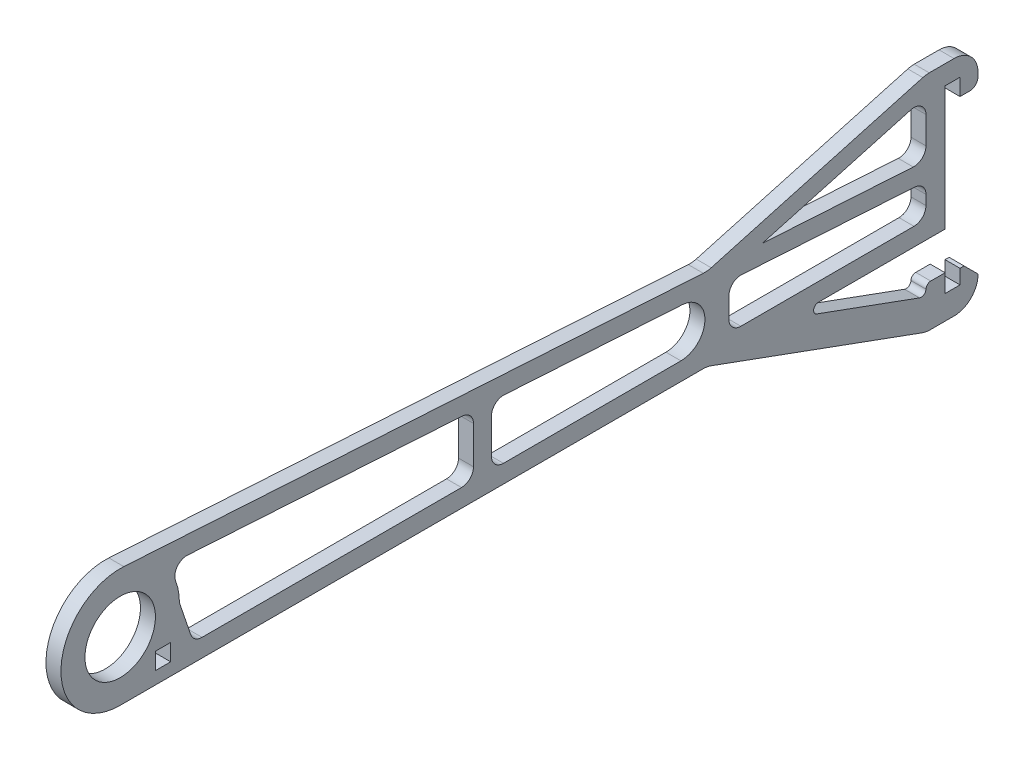
SolidWorks part; units mm, degrees
material "Delrin"
ref_plane "Front Plane" through (0, 0, 0) normal (0, 0, 1) x (1, 0, 0)
ref_plane "Top Plane" through (0, 0, 0) normal (0, 1, 0) x (1, 0, 0)
ref_plane "Right Plane" through (0, 0, 0) normal (1, 0, 0) x (0, 0, -1)
sketch "Sketch1" plane through (0, 0, 0) normal (1, 0, 0) x (0, 0, -1)
  line L0 (0.3859, 6.2619) -> (62.1851, 2.453)
  line L1 (0, -6.2738) -> (62.1851, -6.2738)
  line L2 (85.344, 8.8996) -> (88.3158, 8.8996)
  line L3 (4.7629, 4.0835) -> (85.344, -0.883)
  line L4 (4.5027, -4.3688) -> (85.344, -4.3688)
  line L5 (4.101, 4.1243) -> (87.7175, -1.0293) construction
  line L6 (0, -4.3688) -> (85.344, -4.3688) construction
  line L7 (85.344, -6.2738) -> (85.344, 8.8996) construction
  line L16 (6.2738, 0) -> (7.7597, -4.3688)
  line L17 (39.3251, 1.9533) -> (39.3251, -4.3688)
  line L18 (37.4201, 2.0707) -> (37.4201, -4.3688)
  line L23 (4.2182, 6.0257) -> (87.8347, 0.8721) construction
  line L24 (89.9668, 5.0896) -> (88.9508, 5.0896)
  line L25 (88.9508, 5.0896) -> (88.9508, 6.8676)
  line L26 (88.9508, 6.8676) -> (87.376, 6.8676)
  line L27 (87.376, 6.8676) -> (87.376, -6.2738)
  line L28 (87.376, -12.1824) -> (88.9508, -12.1824)
  line L29 (88.9508, -12.1824) -> (88.9508, -10.6584)
  line L30 (88.9508, -10.6584) -> (89.3826, -10.6584)
  line L31 (90.8558, -12.1316) -> (90.8558, -12.1824)
  line L32 (88.3158, -14.7224) -> (85.344, -14.7224)
  line L33 (85.344, -14.7224) -> (85.344, -6.2738) construction
  line L34 (90.8558, 5.9786) -> (90.8558, 6.3596)
  line L35 (89.3826, -10.6584) -> (90.8558, -12.1316)
  line L36 (64.4711, 0.4035) -> (64.4711, -4.3688)
  line L37 (62.1851, 0.5444) -> (62.1851, -4.3688)
  line L38 (62.1851, 2.453) -> (85.344, 8.8996)
  line L39 (68.0011, 2.0945) -> (85.344, 6.9222)
  line L40 (62.1851, -6.2738) -> (85.344, -14.7224)
  line L41 (71.0788, -6.2738) -> (85.344, -11.4779)
  line L42 (63.2297, -3.4104) -> (86.3886, -11.859) construction
  line L43 (62.696, 0.6178) -> (85.8549, 7.0644) construction
  line L44 (71.0788, -6.2738) -> (85.344, -6.2738)
  line L45 (0, -6.2738) -> (85.344, -6.2738) construction
  line L46 (68.0011, 2.0945) -> (85.344, 1.0256)
  line L47 (62.1851, -4.3688) -> (62.1851, 49995.6312) construction
  line L48 (85.344, 6.9222) -> (85.344, 1.0256)
  line L49 (85.344, -0.883) -> (85.344, -4.3688)
  line L50 (87.376, -12.1824) -> (87.376, -10.2774)
  line L51 (85.344, -6.2738) -> (87.376, -6.2738)
  line L52 (87.376, -10.2774) -> (85.344, -10.2774)
  line L53 (85.344, -10.2774) -> (85.344, -11.4779)
  circle A0 centre (0, 0) radius 3.7338
  circle A1 centre (0, 0) radius 6.2738
  arc A2 (88.3158, 8.8996) -> (90.8558, 6.3596) centre (88.3158, 6.3596) cw
  arc A3 (90.8558, -12.1824) -> (88.3158, -14.7224) centre (88.3158, -12.1824) cw
  arc A4 (90.8558, 5.9786) -> (89.9668, 5.0896) centre (89.9668, 5.9786) cw
  point P47 (90.8558, 8.8996)
  point P50 (90.8558, -14.7224)
  point P53 (90.8558, 5.0896)
  point P54 (90.8558, -10.6584)
  point P56 (90.8558, -10.6584)
  dimension "D1" = 7.4676
  dimension "D2" = 2.54
  dimension "D3" = 5.842
  dimension "D8" = 1.5748
  dimension "D18" = 2.54
  dimension "D19" = 2.54
  dimension "D20" = 0.889
  dimension "D21" = 22.86
  dimension "D5" = 37.4201
  dimension "D10" = 1.905
  dimension "D11" = 1.778
  dimension "D12" = 1.905
  dimension "D4" = 5.3842
  dimension "D9" = 1.5748
  dimension "D14" = 1.524
  dimension "D15" = 3.81
  dimension "D16" = 4.064
  dimension "D17" = 1.905
  dimension "D22" = 19.05
  dimension "D23" = 85.344
  dimension "D24" = 2.032
  dimension "D25" = 2.286
  dimension "D29" = 1.905
  dimension "D6" = 1.905
  dimension "D7" = 1.905
  dimension "D27" = 3.048
  dimension "D28" = 1.905
extrude "Boss-Extrude1" add sketch "Sketch1" along normal blind 1.5875 contours A1 L1 | A1 L4 L16 | L3 L18 L4 L17 | L31 L30 L29 L28 L27 L26 L25 L24 A4 L34 A2 L2 L7 L33 L32 A3 | A1 A0 | L3 L37 L4 L36 region at (0, 3.4205, -31.2278) region at (0, 5.4578, -2.7163) region at (0, -1.1783, -38.3697) region at (0, -3.082, -6.3381) region at (0, -1.9473, -63.3226)
sketch "Sketch2" plane through (0, 0, -87.376) normal (0, 0, -1) x (-1, 0, 0)
  line L0 (-1.5875, 8.8996) -> (0, 8.8996) construction
  line L1 (-1.5875, 6.8676) -> (0, 6.8676) construction
  line L2 (-1.5875, -12.1824) -> (0, -12.1824) construction
  line L3 (-1.5875, -14.7224) -> (0, -14.7224) construction
  line L4 (-1.5875, 8.8996) -> (0, 8.8996)
  line L5 (-1.5875, 6.8676) -> (0, 6.8676)
  line L6 (-1.5875, -12.1824) -> (0, -12.1824)
  line L7 (-1.5875, -14.7224) -> (0, -14.7224)
  line L8 (-1.5875, 8.8996) -> (-1.5875, 6.8676)
  line L9 (0, 8.8996) -> (0, 6.8676)
  line L10 (-1.5875, -12.1824) -> (-1.5875, -14.7224)
  line L11 (0, -12.1824) -> (0, -14.7224)
fillet "Fillet1" radius 2.54 4 edges at (0.7937, 2.453, -62.1851) (0.7937, 8.8996, -85.344) (0.7937, -6.2738, -62.1851) (0.7937, -14.7224, -85.344)
fillet "Fillet2" radius 1.27 12 edges at (0.7937, 4.0835, -4.7629) (0.7937, -4.3688, -7.7597) (0.7937, -4.3688, -37.4201) (0.7937, 2.0707, -37.4201) (0.7937, -4.3688, -39.3251) (0.7937, 1.9533, -39.3251) (0.7937, 0.4035, -64.4711) (0.7937, -4.3688, -64.4711) (0.7937, 1.0256, -85.344) (0.7937, 6.9222, -85.344) (0.7937, -0.883, -85.344) (0.7937, -4.3688, -85.344)
fillet "Fillet3" radius 0.508 2 edges at (0.7937, -6.2738, -71.0788) (0.7937, -11.4779, -85.344)
fillet "Fillet4" radius 0.508 1 edges at (0.7937, -10.2774, -85.344)
sketch "Sketch4" plane through (1.5875, 0, 0) normal (1, 0, 0) x (0, 0, -1)
  line L0 (40.6732, 1.8702) -> (62.1851, 0.5444) construction
  line L1 (62.1851, 0.5444) -> (62.1851, -4.3688) construction
  line L2 (40.5951, -4.3688) -> (62.1851, -4.3688) construction
  line L3 (59.5471, 0.707) -> (62.1851, 0.5444)
  line L4 (62.1851, 0.5444) -> (62.1851, -4.3688)
  line L5 (59.3908, -4.3688) -> (62.1851, -4.3688)
  line L6 (61.9311, -1.8285) -> (62.1851, -1.8285) construction
  line L7 (87.376, 6.8676) -> (87.376, -6.2738) construction
  line L8 (40.5951, -4.3688) -> (62.1851, -4.3688) construction
  arc A0 (59.5471, 0.707) -> (59.3908, -4.3688) centre (59.3908, -1.8285) cw
  dimension "D1" = 0.254
extrude "Boss-Extrude2" add sketch "Sketch4" against normal up to surface (1.5875 mm away) up to face at (0, -0.6692, -20.2932)
sketch "Sketch5" plane through (1.5875, 0, 0) normal (1, 0, 0) x (0, 0, -1)
  line L4 (3.7592, -3.175) -> (3.7592, -4.953)
  line L5 (3.7592, -4.953) -> (5.3467, -4.953)
  line L6 (5.3467, -4.953) -> (5.3467, -3.175)
  line L7 (5.3467, -3.175) -> (3.7592, -3.175)
  line L8 (3.7592, -3.175) -> (3.7592, -4.953)
  line L9 (3.7592, -4.953) -> (5.3467, -4.953)
  line L10 (5.3467, -4.953) -> (5.3467, -3.175)
  line L11 (5.3467, -3.175) -> (3.7592, -3.175)
  dimension "D1" = 0
extrude "Cut-Extrude1" cut sketch "Sketch5" against normal up to next
